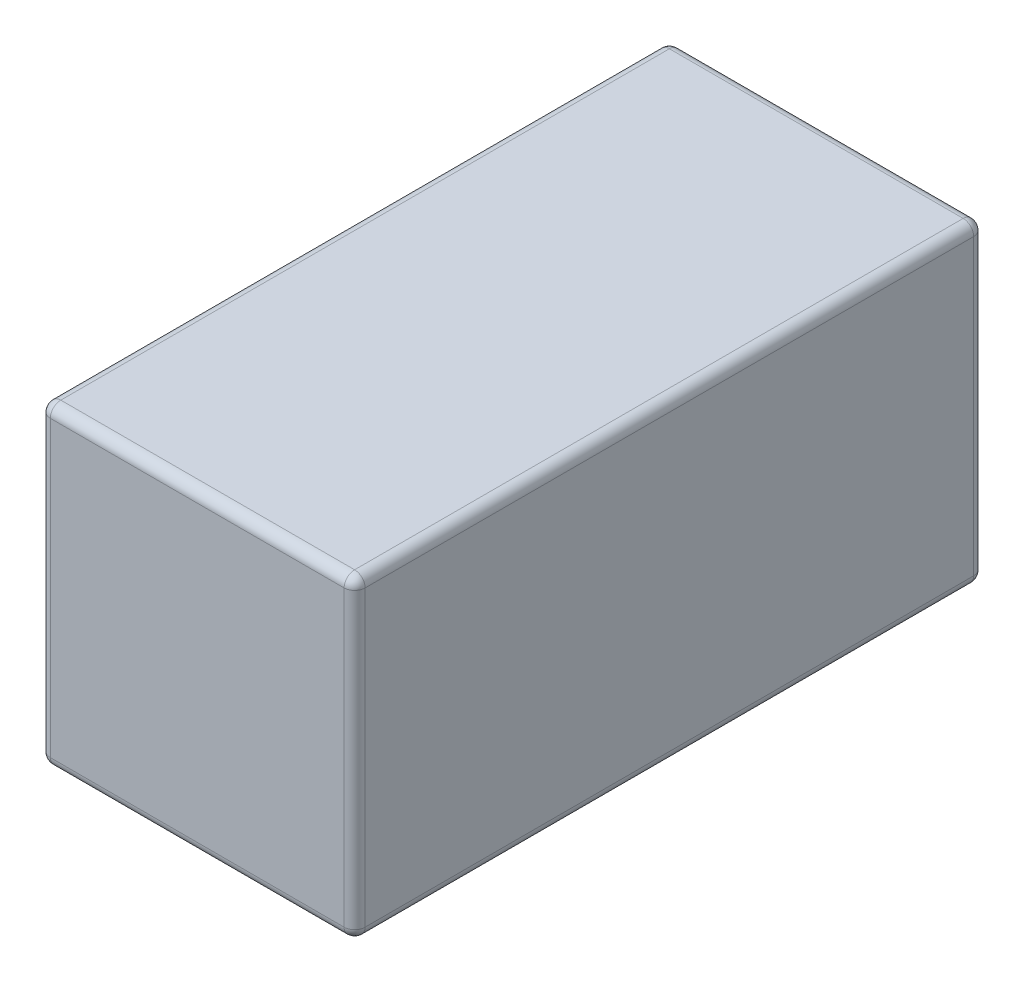
SolidWorks part; units mm, degrees
material "AISI 1045 Steel, cold drawn"
ref_plane "Front Plane" through (0, 0, 0) normal (0, 0, 1) x (1, 0, 0)
ref_plane "Top Plane" through (0, 0, 0) normal (0, 1, 0) x (1, 0, 0)
ref_plane "Right Plane" through (0, 0, 0) normal (1, 0, 0) x (0, 0, -1)
sketch "Sketch1" plane through (0, 0, 0) normal (0, 0, 1) x (1, 0, 0)
  line L3 (3, -3) -> (-3, -3)
  line L4 (3, -3) -> (3, 3)
  line L5 (3, 3) -> (-3, 3)
  line L6 (-3, -3) -> (-3, 3)
  line L7 (3, -3) -> (-3, 3) construction
  line L8 (3, 3) -> (-3, -3) construction
  point P0 (0, 0)
  dimension "Width" = 6
  dimension "Height" = 6
sketch "Sketch2" plane through (0, 0, 0) normal (1, 0, 0) x (0, 0, -1)
  line L2 (6, -3) -> (-6, -3)
  line L3 (6, -3) -> (6, 3)
  line L4 (6, 3) -> (-6, 3)
  line L5 (-6, -3) -> (-6, 3)
  line L6 (6, -3) -> (-6, 3) construction
  line L7 (6, 3) -> (-6, -3) construction
  point P0 (0, 0)
  point P4 (0, 0)
  dimension "Length" = 12
sketch "Sketch3" plane through (0, 0, 0) normal (0, 0, 1) x (1, 0, 0)
  line L0 (3, -3) -> (3, 3) construction
  line L5 (3, -3) -> (-3, -3) construction
  line L6 (-3, -3) -> (-3, 3) construction
  line L7 (3, 3) -> (-3, 3) construction
  line L8 (3, -3) -> (3, 3)
  line L9 (3, -3) -> (-3, -3)
  line L10 (-3, -3) -> (-3, 3)
  line L11 (3, 3) -> (-3, 3)
extrude "Boss-Extrude1" add sketch "Sketch3" along normal up to vertex (6 mm away) and the other way up to vertex (6 mm away) up to point (0, 3, 6) other way up to point (0, 3, -6)
fillet "Fillet2" radius 0.2 12 edges at (-3, 0, -6) (0, -3, -6) (-3, 3, 0) (0, 3, -6) (3, 3, 0) (3, 0, -6) (3, -3, 0) (-3, 0, 6) (0, 3, 6) (3, 0, 6) (0, -3, 6) (-3, -3, 0)
ref_plane "Contact Plane 1" through (0, 0, 6) normal (0, 0, 1) x (1, 0, 0)
ref_plane "Contact Plane 2" through (0, 0, -6) normal (0, 0, 1) x (1, 0, 0)
ref_axis "Center Axis 1" through (0, 0, -4.4) along (0, 0, 1)
